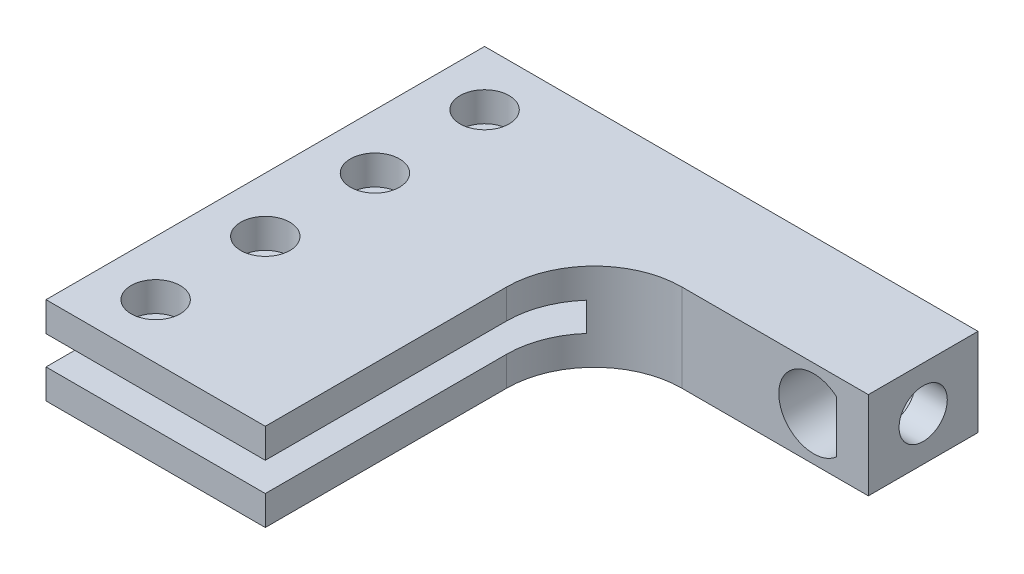
SolidWorks part; units mm, degrees
ref_plane "Front Plane" through (0, 0, 0) normal (0, 0, 1) x (1, 0, 0)
ref_plane "Top Plane" through (0, 0, 0) normal (0, 1, 0) x (1, 0, 0)
ref_plane "Right Plane" through (0, 0, 0) normal (1, 0, 0) x (0, 0, -1)
sketch "Sketch1" plane through (0, 0, 0) normal (0, 1, 0) x (1, 0, 0)
  line L0 (-33.097, 5.3879) -> (-20.397, 5.3879)
  line L2 (-20.397, 5.3879) -> (-4.522, 5.3879)
  line L3 (-4.522, 5.3879) -> (-4.522, -0.9621)
  line L4 (-4.522, -0.9621) -> (-20.397, -0.9621)
  line L5 (-20.397, -0.9621) -> (-20.397, -20.0121)
  line L6 (-20.397, -20.0121) -> (-33.097, -20.0121)
  line L7 (-33.097, -20.0121) -> (-33.097, 5.3879)
  dimension "D1" = 25.4
  dimension "D2" = 12.7
  dimension "D3" = 6.35
  dimension "D4" = 15.875
extrude "Boss-Extrude1" add sketch "Sketch1" along normal blind 5.08
sketch "Sketch2" plane through (-33.097, 0, 0) normal (-1, 0, 0) x (0, 0, 1)
  line L0 (-5.3879, 5.08) -> (-5.3879, 0) construction
  line L1 (-5.3879, 3.3735) -> (20.0121, 3.3735)
  line L2 (-5.3879, 3.3735) -> (-5.3879, 1.7065)
  line L3 (-5.3879, 1.7065) -> (20.0121, 1.7065)
  line L4 (20.0121, 3.3735) -> (20.0121, 1.7065)
  line L5 (20.0121, 5.08) -> (20.0121, 0) construction
  line L6 (7.3121, 5.08) -> (7.3121, 3.3735) construction
  line L7 (-5.3879, 5.08) -> (20.0121, 5.08) construction
  line L8 (7.3121, 1.7065) -> (7.3121, 0) construction
  line L9 (-5.3879, 0) -> (20.0121, 0) construction
  dimension "D1" = 1.6669
extrude "Cut-Extrude1" cut sketch "Sketch2" against normal blind 13.97
sketch "Sketch3" plane through (0, 5.08, 0) normal (0, 1, 0) x (1, 0, 0)
  line L0 (-33.097, 5.3879) -> (-33.097, -20.0121) construction
  line L2 (-33.097, -20.0121) -> (-20.397, -20.0121) construction
  circle A0 centre (-29.922, -16.8371) radius 1.4224
  circle A1 centre (-29.922, -10.4871) radius 1.4224
  circle A2 centre (-29.922, -4.1371) radius 1.4224
  circle A3 centre (-29.922, 2.2129) radius 1.4224
  dimension "D1" = 2.8448
  dimension "D4" = 4
  dimension "D2" = 3.175
  dimension "D3" = 3.175
  dimension "D5" = 6.35
extrude "Cut-Extrude2" cut sketch "Sketch3" against normal blind 12.7
sketch "Sketch5" plane through (0, 0, 0.9621) normal (0, 0, 1) x (1, 0, 0)
  line L0 (-4.522, 5.08) -> (-4.522, 0) construction
  line L1 (-20.397, 5.08) -> (-4.522, 5.08) construction
  line L2 (-9.7086, 2.54) -> (-9.7086, 5.4864) construction
  line L3 (-6.3558, 1.0406) -> (-6.3558, 4.0394)
  arc A0 (-6.3558, 4.0394) -> (-6.3558, 1.0406) centre (-7.697, 2.54) ccw
  dimension "D1" = 4.0234
  dimension "D2" = 3.175
  dimension "D3" = 2.54
  dimension "D4" = 3.3528
extrude "Cut-Extrude3" cut sketch "Sketch5" against normal blind 12.7
fillet "Fillet3" radius 5.08 2 edges at (-20.397, 4.2267, 0.9621) (-20.397, 0.8533, 0.9621)
sketch "Sketch6" plane through (-4.522, 0, 0) normal (1, 0, 0) x (0, 0, -1)
  line L0 (2.2129, 5.08) -> (2.2129, 0) construction
  line L1 (3.6353, 5.08) -> (0.7905, 5.08) construction
  line L2 (-0.9621, 0) -> (5.3879, 0) construction
  circle A0 centre (2.2129, 2.54) radius 1.397
  point P8 (0, 0)
  point P9 (2.2129, 2.54)
  dimension "D1" = 2.794
extrude "Cut-Extrude4" cut sketch "Sketch6" against normal up to next
equation "\"bolt_hole\"= .112in'holes for screws"
